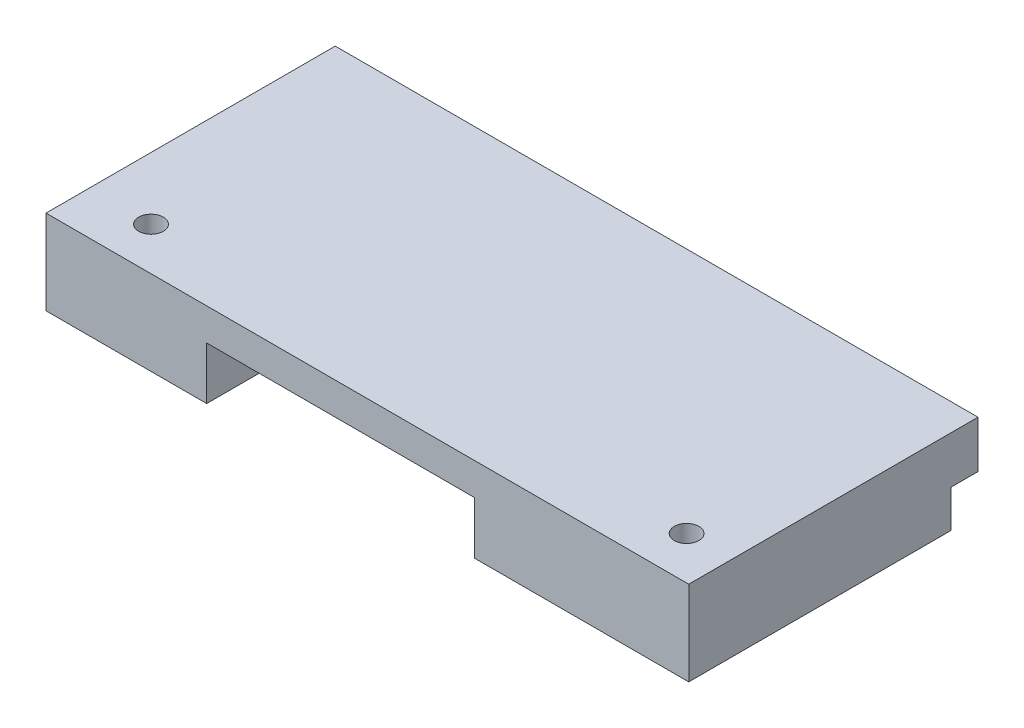
SolidWorks part; units mm, degrees
ref_plane "Płaszczyzna przednia" through (0, 0, 0) normal (0, 0, 1) x (1, 0, 0)
ref_plane "Płaszczyzna górna" through (0, 0, 0) normal (0, 1, 0) x (1, 0, 0)
ref_plane "Płaszczyzna prawa" through (0, 0, 0) normal (1, 0, 0) x (0, 0, -1)
sketch "Sketch1" plane through (0, 0, 0) normal (0, 1, 0) x (1, 0, 0)
  line L1 (-30, -1.25) -> (30, -1.25)
  line L2 (-30, -1.25) -> (-30, 1.25)
  line L3 (-30, 1.25) -> (30, 1.25)
  line L4 (30, -1.25) -> (30, 1.25)
  line L5 (-30, -1.25) -> (30, 1.25) construction
  line L6 (-30, 1.25) -> (30, -1.25) construction
  point P0 (0, 0)
  dimension "D1" = 2.5
  dimension "D2" = 60
extrude "Boss-Extrude1" add sketch "Sketch1" along normal blind 2.5
sketch "Sketch2" plane through (0, 2.5, 0) normal (0, 1, 0) x (1, 0, 0)
  line L0 (30, -1.25) -> (30, 1.25) construction
  line L1 (-30, -1.25) -> (30, -1.25)
  line L2 (-30, -1.25) -> (-30, 3.75)
  line L3 (-30, 3.75) -> (30, 3.75)
  line L4 (30, -1.25) -> (30, 3.75)
  line L9 (30, 1.25) -> (-30, 1.25) construction
  dimension "D1" = 2.5
extrude "Boss-Extrude2" add sketch "Sketch2" along normal blind 3
sketch "Sketch5" plane through (0, 0, 1.25) normal (0, 0, 1) x (1, 0, 0)
  line L4 (-30, 0) -> (30, 0)
  line L5 (30, 0) -> (30, 5.5)
  line L6 (30, 5.5) -> (-30, 5.5)
  line L7 (-30, 5.5) -> (-30, 0)
  line L8 (-30, 0) -> (30, 0)
  line L9 (30, 0) -> (30, 5.5)
  line L10 (30, 5.5) -> (-30, 5.5)
  line L11 (-30, 5.5) -> (-30, 0)
  dimension "D1" = 0
extrude "Boss-Extrude4" add sketch "Sketch5" along normal blind 22
sketch "Sketch6" plane through (0, 5.5, 0) normal (0, 1, 0) x (1, 0, 0)
  line L4 (-30, 3.75) -> (-30, -23.25)
  line L5 (-30, -23.25) -> (30, -23.25)
  line L6 (30, -23.25) -> (30, 3.75)
  line L7 (30, 3.75) -> (-30, 3.75)
  line L8 (-30, 3.75) -> (-30, -23.25)
  line L9 (-30, -23.25) -> (30, -23.25)
  line L10 (30, -23.25) -> (30, 3.75)
  line L11 (30, 3.75) -> (-30, 3.75)
  dimension "D1" = 0
extrude "Boss-Extrude5" add sketch "Sketch6" along normal blind 2.4
hole_wizard "Ø2.3 (2.3) Diameter Hole1" positions "Sketch7" profile "Sketch8" hole size "Ø2.3" standard "DIN" end condition through all
sketch "Sketch7" plane through (0, 7.9, 0) normal (0, 1, 0) x (1, 0, 0)
  line L1 (30, -23.25) -> (30, 3.75) construction
  line L2 (-30, -23.25) -> (30, -23.25) construction
  line L3 (25.8, -19.25) -> (-24.2, -19.25)
  point P0 (-24.2, -19.25)
  point P2 (25.8, -19.25)
  dimension "D1" = 50
  dimension "D2" = 4
  dimension "D3" = 4.2
sketch "Sketch8" plane through (-24.2, 7.9, 19.25) normal (1, 0, 0) x (0, 0, 1)
  line L0 (0, 0) -> (0, 7.9)
  line L1 (0, 7.9) -> (1.15, 7.9)
  line L2 (1.15, 7.9) -> (1.15, 0)
  line L5 (1.15, 0) -> (0, 0)
  line L11 (0, -6.35) -> (0, 107.95) construction
  dimension "Thru Hole Dia." = 2.3
  dimension "Thru Hole Depth" = 7.9
sketch "Sketch9" plane through (0, 0, -3.75) normal (0, 0, -1) x (-1, 0, 0)
  line L1 (-10, 4.9) -> (15, 4.9)
  line L2 (-10, 4.9) -> (-10, -4.7096)
  line L3 (-10, -4.7096) -> (15, -4.7096)
  line L4 (15, 4.9) -> (15, -4.7096)
  line L5 (30, 7.9) -> (30, 2.5) construction
  line L7 (-30, 7.9) -> (30, 7.9) construction
  dimension "D1" = 25
  dimension "D2" = 15
  dimension "D3" = 3
extrude "Cut-Extrude1" cut sketch "Sketch9" against normal through all
sketch "Sketch10" plane through (0, 0, -1.25) normal (0, 0, -1) x (-1, 0, 0)
  line L0 (30, 7.9) -> (30, 2.5) construction
  line L1 (-30, 0) -> (30, 0)
  line L2 (-30, 0) -> (-30, 3.5)
  line L3 (-30, 3.5) -> (30, 3.5)
  line L4 (30, 0) -> (30, 3.5)
  dimension "D1" = 3.5
extrude "Cut-Extrude2" cut sketch "Sketch10" along normal through all
